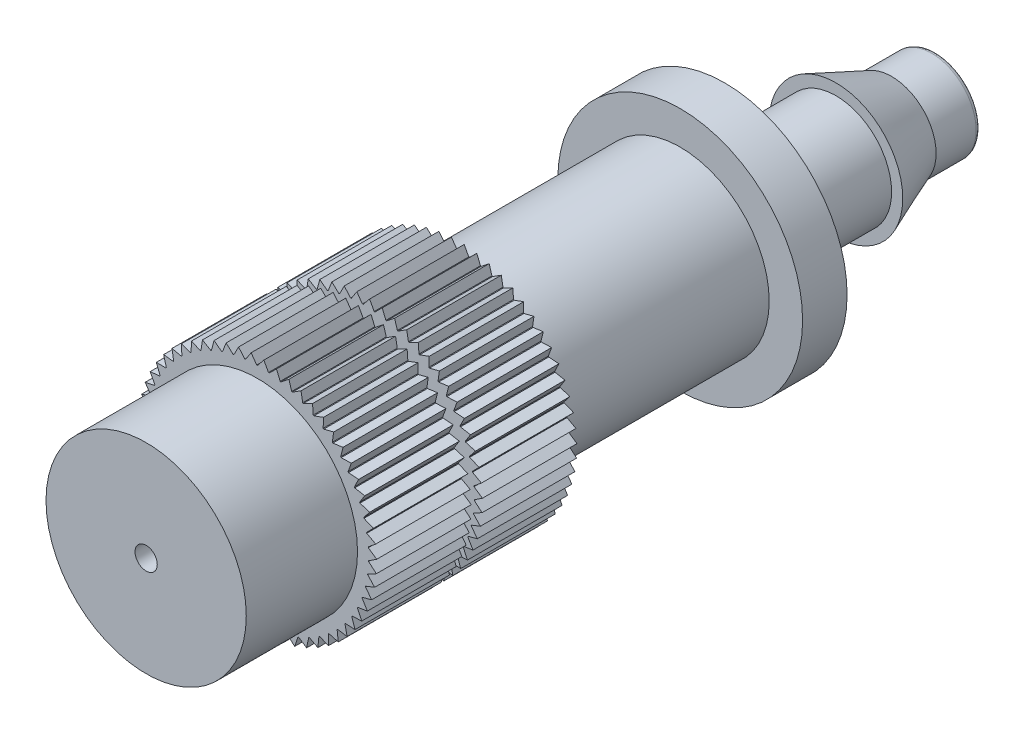
SolidWorks part; units mm, degrees
material "ABS"
ref_plane "Front Plane" through (0, 0, 0) normal (0, 0, 1) x (1, 0, 0)
ref_plane "Top Plane" through (0, 0, 0) normal (0, 1, 0) x (1, 0, 0)
ref_plane "Right Plane" through (0, 0, 0) normal (1, 0, 0) x (0, 0, -1)
sketch "Sketch1" plane through (0, 0, 0) normal (0, 0, 1) x (1, 0, 0)
  circle A0 centre (0, 0) radius 2
  dimension "D1" = 4
extrude "Boss-Extrude1" add sketch "Sketch1" along normal blind 2
sketch "Sketch3" plane through (0, 0, 0) normal (0, 1, 0) x (1, 0, 0)
  line L0 (0, -4.5) -> (0, -2)
  line L1 (-2, -2) -> (2, -2) construction
  line L2 (0, -2) -> (-2, -2)
  line L3 (-2, -2) -> (-3, -4.5)
  line L4 (-3, -4.5) -> (0, -4.5)
  dimension "D1" = 2.5
  dimension "D2" = 3
revolve "Revolve1" add sketch "Sketch3" angle 360 about L0
sketch "Sketch4" plane through (0, 0, 4.5) normal (0, 0, 1) x (1, 0, 0)
  circle A0 centre (0, 0) radius 2.5
  dimension "D1" = 5
extrude "Boss-Extrude2" add sketch "Sketch4" along normal blind 5
sketch "Sketch5" plane through (0, 0, 9.5) normal (0, 0, 1) x (1, 0, 0)
  circle A0 centre (0, 0) radius 5.5
  dimension "D1" = 11
extrude "Boss-Extrude3" add sketch "Sketch5" along normal blind 2
sketch "Sketch6" plane through (0, 0, 11.5) normal (0, 0, 1) x (1, 0, 0)
  circle A0 centre (0, 0) radius 4
  dimension "D1" = 8
extrude "Boss-Extrude4" add sketch "Sketch6" along normal blind 10
sketch "Sketch7" plane through (0, 0, 21.5) normal (0, 0, 1) x (1, 0, 0)
  line L0 (0, 5) -> (0.291, 5.3547)
  line L1 (0.291, 5.3547) -> (0.4994, 4.975)
  line L2 (0, 5) -> (0.4994, 4.975)
  line L3 (0.5315, 4.9717) -> (1.0254, 4.8937)
  line L4 (0.8586, 5.2934) -> (1.0254, 4.8937)
  line L5 (0.5315, 4.9717) -> (0.8586, 5.2934)
  line L6 (1.0569, 4.887) -> (1.5397, 4.757)
  line L7 (1.4163, 5.1722) -> (1.5397, 4.757)
  line L8 (1.0569, 4.887) -> (1.4163, 5.1722)
  line L9 (1.5704, 4.747) -> (2.0366, 4.5664)
  line L10 (1.9581, 4.9923) -> (2.0366, 4.5664)
  line L11 (1.5704, 4.747) -> (1.9581, 4.9923)
  line L12 (2.0661, 4.5532) -> (2.5105, 4.3241)
  line L13 (2.4777, 4.7559) -> (2.5105, 4.3241)
  line L14 (2.0661, 4.5532) -> (2.4777, 4.7559)
  line L15 (2.5383, 4.3078) -> (2.9559, 4.0327)
  line L16 (2.9691, 4.4656) -> (2.9559, 4.0327)
  line L17 (2.5383, 4.3078) -> (2.9691, 4.4656)
  line L18 (2.9818, 4.0136) -> (3.3678, 3.6957)
  line L19 (3.427, 4.1247) -> (3.3678, 3.6957)
  line L20 (2.9818, 4.0136) -> (3.427, 4.1247)
  line L21 (3.3916, 3.6739) -> (3.7415, 3.3168)
  line L22 (3.846, 3.7371) -> (3.7415, 3.3168)
  line L23 (3.3916, 3.6739) -> (3.846, 3.7371)
  line L24 (3.7629, 3.2926) -> (4.0729, 2.9003)
  line L25 (4.2214, 3.3071) -> (4.0729, 2.9003)
  line L26 (3.7629, 3.2926) -> (4.2214, 3.3071)
  line L27 (4.0915, 2.8739) -> (4.3581, 2.4509)
  line L28 (4.5491, 2.8397) -> (4.3581, 2.4509)
  line L29 (4.0915, 2.8739) -> (4.5491, 2.8397)
  line L30 (4.3738, 2.4228) -> (4.5939, 1.9738)
  line L31 (4.8251, 2.34) -> (4.5939, 1.9738)
  line L32 (4.3738, 2.4228) -> (4.8251, 2.34)
  line L33 (4.6066, 1.9441) -> (4.7777, 1.4743)
  line L34 (5.0465, 1.8139) -> (4.7777, 1.4743)
  line L35 (4.6066, 1.9441) -> (5.0465, 1.8139)
  line L36 (4.7871, 1.4435) -> (4.9073, 0.9581)
  line L37 (5.2107, 1.2672) -> (4.9073, 0.9581)
  line L38 (4.7871, 1.4435) -> (5.2107, 1.2672)
  line L39 (4.9134, 0.9264) -> (4.9814, 0.4311)
  line L40 (5.3159, 0.7062) -> (4.9814, 0.4311)
  line L41 (4.9134, 0.9264) -> (5.3159, 0.7062)
  line L42 (4.9841, 0.3989) -> (4.999, -0.1008)
  line L43 (5.3609, 0.1371) -> (4.999, -0.1008)
  line L44 (4.9841, 0.3989) -> (5.3609, 0.1371)
  line L45 (4.9982, -0.1331) -> (4.9599, -0.6316)
  line L46 (5.3451, -0.4335) -> (4.9599, -0.6316)
  line L47 (4.9982, -0.1331) -> (5.3451, -0.4335)
  line L48 (4.9558, -0.6636) -> (4.8647, -1.1553)
  line L49 (5.2687, -0.9992) -> (4.8647, -1.1553)
  line L50 (4.9558, -0.6636) -> (5.2687, -0.9992)
  line L51 (4.8571, -1.1866) -> (4.7143, -1.6658)
  line L52 (5.1327, -1.5535) -> (4.7143, -1.6658)
  line L53 (4.8571, -1.1866) -> (5.1327, -1.5535)
  line L54 (4.7035, -1.6962) -> (4.5106, -2.1575)
  line L55 (4.9384, -2.0903) -> (4.5106, -2.1575)
  line L56 (4.7035, -1.6962) -> (4.9384, -2.0903)
  line L57 (4.4966, -2.1865) -> (4.2557, -2.6247)
  line L58 (4.6883, -2.6034) -> (4.2557, -2.6247)
  line L59 (4.4966, -2.1865) -> (4.6883, -2.6034)
  line L60 (4.2387, -2.6521) -> (3.9526, -3.0622)
  line L61 (4.385, -3.087) -> (3.9526, -3.0622)
  line L62 (4.2387, -2.6521) -> (4.385, -3.087)
  line L63 (3.9328, -3.0876) -> (3.6047, -3.465)
  line L64 (4.032, -3.5356) -> (3.6047, -3.465)
  line L65 (3.9328, -3.0876) -> (4.032, -3.5356)
  line L66 (3.5823, -3.4882) -> (3.216, -3.8285)
  line L67 (3.6334, -3.9441) -> (3.216, -3.8285)
  line L68 (3.5823, -3.4882) -> (3.6334, -3.9441)
  line L69 (3.1912, -3.8492) -> (2.7908, -4.1486)
  line L70 (3.1936, -4.308) -> (2.7908, -4.1486)
  line L71 (3.1912, -3.8492) -> (3.1936, -4.308)
  line L72 (2.764, -4.1666) -> (2.334, -4.4218)
  line L73 (2.7176, -4.623) -> (2.334, -4.4218)
  line L74 (2.764, -4.1666) -> (2.7176, -4.623)
  line L75 (2.3055, -4.4368) -> (1.8508, -4.6448)
  line L76 (2.2108, -4.8857) -> (1.8508, -4.6448)
  line L77 (2.3055, -4.4368) -> (2.2108, -4.8857)
  line L78 (1.8208, -4.6567) -> (1.3466, -4.8153)
  line L79 (1.6789, -5.093) -> (1.3466, -4.8153)
  line L80 (1.8208, -4.6567) -> (1.6789, -5.093)
  line L81 (1.3155, -4.8238) -> (0.8272, -4.9311)
  line L82 (1.1281, -5.2426) -> (0.8272, -4.9311)
  line L83 (1.3155, -4.8238) -> (1.1281, -5.2426)
  line L84 (0.7953, -4.9363) -> (0.2983, -4.9911)
  line L85 (0.5644, -5.3328) -> (0.2983, -4.9911)
  line L86 (0.7953, -4.9363) -> (0.5644, -5.3328)
  line L87 (0.2661, -4.9929) -> (-0.2339, -4.9945)
  line L88 (-0.0056, -5.3626) -> (-0.2339, -4.9945)
  line L89 (0.2661, -4.9929) -> (-0.0056, -5.3626)
  line L90 (-0.2661, -4.9929) -> (-0.7634, -4.9414)
  line L91 (-0.5756, -5.3316) -> (-0.7634, -4.9414)
  line L92 (-0.2661, -4.9929) -> (-0.5756, -5.3316)
  line L93 (-0.7953, -4.9363) -> (-1.2844, -4.8322)
  line L94 (-1.1391, -5.2402) -> (-1.2844, -4.8322)
  line L95 (-0.7953, -4.9363) -> (-1.1391, -5.2402)
  line L96 (-1.3155, -4.8238) -> (-1.7907, -4.6683)
  line L97 (-1.6896, -5.0895) -> (-1.7907, -4.6683)
  line L98 (-1.3155, -4.8238) -> (-1.6896, -5.0895)
  line L99 (-1.8208, -4.6567) -> (-2.2768, -4.4515)
  line L100 (-2.221, -4.8811) -> (-2.2768, -4.4515)
  line L101 (-1.8208, -4.6567) -> (-2.221, -4.8811)
  line L102 (-2.3055, -4.4368) -> (-2.7371, -4.1843)
  line L103 (-2.7273, -4.6173) -> (-2.7371, -4.1843)
  line L104 (-2.3055, -4.4368) -> (-2.7273, -4.6173)
  line L105 (-2.764, -4.1666) -> (-3.1663, -3.8697)
  line L106 (-3.2026, -4.3013) -> (-3.1663, -3.8697)
  line L107 (-2.764, -4.1666) -> (-3.2026, -4.3013)
  line L108 (-3.1912, -3.8492) -> (-3.5597, -3.5112)
  line L109 (-3.6417, -3.9365) -> (-3.5597, -3.5112)
  line L110 (-3.1912, -3.8492) -> (-3.6417, -3.9365)
  line L111 (-3.5823, -3.4882) -> (-3.9128, -3.1129)
  line L112 (-4.0394, -3.5271) -> (-3.9128, -3.1129)
  line L113 (-3.5823, -3.4882) -> (-4.0394, -3.5271)
  line L114 (-3.9328, -3.0876) -> (-4.2215, -2.6794)
  line L115 (-4.3915, -3.0778) -> (-4.2215, -2.6794)
  line L116 (-3.9328, -3.0876) -> (-4.3915, -3.0778)
  line L117 (-4.2387, -2.6521) -> (-4.4824, -2.2155)
  line L118 (-4.6937, -2.5935) -> (-4.4824, -2.2155)
  line L119 (-4.2387, -2.6521) -> (-4.6937, -2.5935)
  line L120 (-4.4966, -2.1865) -> (-4.6925, -1.7265)
  line L121 (-4.9428, -2.0799) -> (-4.6925, -1.7265)
  line L122 (-4.4966, -2.1865) -> (-4.9428, -2.0799)
  line L123 (-4.7035, -1.6962) -> (-4.8494, -1.218)
  line L124 (-5.1359, -1.5428) -> (-4.8494, -1.218)
  line L125 (-4.7035, -1.6962) -> (-5.1359, -1.5428)
  line L126 (-4.8571, -1.1866) -> (-4.9514, -0.6956)
  line L127 (-5.2708, -0.9881) -> (-4.9514, -0.6956)
  line L128 (-4.8571, -1.1866) -> (-5.2708, -0.9881)
  line L129 (-4.9558, -0.6636) -> (-4.9973, -0.1654)
  line L130 (-5.346, -0.4223) -> (-4.9973, -0.1654)
  line L131 (-4.9558, -0.6636) -> (-5.346, -0.4223)
  line L132 (-4.9982, -0.1331) -> (-4.9865, 0.3668)
  line L133 (-5.3606, 0.1484) -> (-4.9865, 0.3668)
  line L134 (-4.9982, -0.1331) -> (-5.3606, 0.1484)
  line L135 (-4.9841, 0.3989) -> (-4.9193, 0.8947)
  line L136 (-5.3144, 0.7173) -> (-4.9193, 0.8947)
  line L137 (-4.9841, 0.3989) -> (-5.3144, 0.7173)
  line L138 (-4.9134, 0.9264) -> (-4.7963, 1.4125)
  line L139 (-5.2081, 1.2782) -> (-4.7963, 1.4125)
  line L140 (-4.9134, 0.9264) -> (-5.2081, 1.2782)
  line L141 (-4.7871, 1.4435) -> (-4.619, 1.9144)
  line L142 (-5.0427, 1.8245) -> (-4.619, 1.9144)
  line L143 (-4.7871, 1.4435) -> (-5.0427, 1.8245)
  line L144 (-4.6066, 1.9441) -> (-4.3894, 2.3945)
  line L145 (-4.8202, 2.3502) -> (-4.3894, 2.3945)
  line L146 (-4.6066, 1.9441) -> (-4.8202, 2.3502)
  line L147 (-4.3738, 2.4228) -> (-4.11, 2.8475)
  line L148 (-4.5431, 2.8492) -> (-4.11, 2.8475)
  line L149 (-4.3738, 2.4228) -> (-4.5431, 2.8492)
  line L150 (-4.0915, 2.8739) -> (-3.784, 3.2682)
  line L151 (-4.2145, 3.316) -> (-3.784, 3.2682)
  line L152 (-4.0915, 2.8739) -> (-4.2145, 3.316)
  line L153 (-3.7629, 3.2926) -> (-3.4152, 3.6519)
  line L154 (-3.8382, 3.7452) -> (-3.4152, 3.6519)
  line L155 (-3.7629, 3.2926) -> (-3.8382, 3.7452)
  line L156 (-3.3916, 3.6739) -> (-3.0077, 3.9942)
  line L157 (-3.4183, 4.1319) -> (-3.0077, 3.9942)
  line L158 (-3.3916, 3.6739) -> (-3.4183, 4.1319)
  line L159 (-2.9818, 4.0136) -> (-2.5661, 4.2913)
  line L160 (-2.9598, 4.4718) -> (-2.5661, 4.2913)
  line L161 (-2.9818, 4.0136) -> (-2.9598, 4.4718)
  line L162 (-2.5383, 4.3078) -> (-2.0954, 4.5397)
  line L163 (-2.4677, 4.7611) -> (-2.0954, 4.5397)
  line L164 (-2.5383, 4.3078) -> (-2.4677, 4.7611)
  line L165 (-2.0661, 4.5532) -> (-1.601, 4.7368)
  line L166 (-1.9476, 4.9964) -> (-1.601, 4.7368)
  line L167 (-2.0661, 4.5532) -> (-1.9476, 4.9964)
  line L168 (-1.5704, 4.747) -> (-1.0884, 4.8801)
  line L169 (-1.4055, 5.1752) -> (-1.0884, 4.8801)
  line L170 (-1.5704, 4.747) -> (-1.4055, 5.1752)
  line L171 (-1.0569, 4.887) -> (-0.5635, 4.9681)
  line L172 (-0.8474, 5.2952) -> (-0.5635, 4.9681)
  line L173 (-1.0569, 4.887) -> (-0.8474, 5.2952)
  line L174 (-0.5315, 4.9717) -> (-0.0323, 4.9999)
  line L175 (-0.2798, 5.3553) -> (-0.0323, 4.9999)
  line L176 (-0.5315, 4.9717) -> (-0.2798, 5.3553)
  circle A0 centre (0, 0) radius 5
  point P90 (0, 0)
  circle M2 centre (0, 0) radius 4
  dimension "D1" = 10
  dimension "D2" = 0.5
  dimension "D3" = 59
fillet "Fillet2" radius 0.2 1 edges at (2, 0, 0)
extrude "Boss-Extrude5" add sketch "Sketch7" along normal blind 9 contours A0 L172 L173 | A0 L166 L167 | A0 L175 L176 | A0 L1 L0 | A0 L13 L14 | A0 L19 L20 | A0 L16 L17 | A0 L22 L23 | A0 L25 L26 | A0 L28 L29 | A0 L31 L32 | A0 L40 L41 | A0 L43 L44 | A0 L46 L47 | A0 L52 L53 | A0 L55 L56 | A0 L58 L59 | A0 L61 L62 | A0 L64 L65 | A0 L163 L164 | A0 L160 L161 | A0 L157 L158 | A0 L154 L155 | A0 L151 L152 | A0 L148 L149 | A0 L142 L143 | A0 L139 L140 | A0 L136 L137 | A0 L133 L134 | A0 L130 L131 | A0 L127 L128 | A0 L112 L113 | A0 L115 L116 | A0 L118 L119 | A0 L121 L122 | A0 L124 L125 | A0 L109 L110 | A0 L106 L107 | A0 L103 L104 | A0 L100 L101 | A0 L97 L98 | A0 L91 L92 | A0 L85 L86 | A0 L82 L83 | A0 L79 L80 | A0 L76 L77 | A0 L73 L74 | A0 L70 L71 | A0 L67 L68 | L42 A0 L39 L36 L33 L30 L27 L24 L21 L18 L15 L12 L9 L6 L3 L2 L174 L171 L168 L165 L162 L159 L156 L153 L150 L147 L144 | M2 | L168 L169 L170 | L4 L3 L5 | L7 L6 L8 | L10 L9 L11 | L33 L34 L35 | L36 L37 L38 | L48 L49 L50 | L145 L144 L146 | L93 L94 L95 | A0 | L87 L88 L89 region at (0.2638, 5.1127, 21.5) region at (0.2426, 4.8463, 21.5) region at (-0.2812, 5.1118, 21.5) region at (-0.8229, 5.0529, 21.5) region at (-1.8724, 4.7648, 21.5) region at (2.3528, 4.5468, 21.5) region at (-2.3683, 4.5388, 21.5) region at (2.8228, 4.2709, 21.5) region at (-2.8373, 4.2613, 21.5) region at (3.2608, 3.9467, 21.5) region at (-3.2742, 3.9356, 21.5) region at (3.6618, 3.5777, 21.5) region at (-3.6739, 3.5653, 21.5) region at (4.0214, 3.1682, 21.5) region at (-4.0321, 3.1546, 21.5) region at (4.3353, 2.7228, 21.5) region at (-4.3446, 2.7081, 21.5) region at (4.6002, 2.2466, 21.5) region at (-4.8188, 1.7285, 21.5) region at (-4.9753, 1.2065, 21.5) region at (5.073, 0.6881, 21.5) region at (-5.0753, 0.6709, 21.5) region at (5.1174, 0.145, 21.5) region at (-5.1179, 0.1276, 21.5) region at (5.1038, -0.3998, 21.5) region at (-5.1025, -0.4171, 21.5) region at (-5.0292, -0.9571, 21.5) region at (4.904, -1.4696, 21.5) region at (-4.899, -1.4863, 21.5) region at (4.72, -1.9826, 21.5) region at (-4.7132, -1.9986, 21.5) region at (4.4825, -2.473, 21.5) region at (-4.4741, -2.4883, 21.5) region at (4.1943, -2.9355, 21.5) region at (-4.1843, -2.9497, 21.5) region at (3.8585, -3.3647, 21.5) region at (-3.847, -3.3778, 21.5) region at (3.479, -3.7558, 21.5) region at (-3.4662, -3.7676, 21.5) region at (3.0601, -4.1043, 21.5) region at (-3.0461, -4.1146, 21.5) region at (2.6065, -4.4063, 21.5) region at (-2.5915, -4.4151, 21.5) region at (2.1233, -4.6584, 21.5) region at (-2.1075, -4.6656, 21.5) region at (1.6162, -4.8577, 21.5) region at (-1.5996, -4.8631, 21.5) region at (1.0907, -5.0019, 21.5) region at (0.5528, -5.0895, 21.5) region at (-0.5355, -5.0914, 21.5) region at (0, 0, 21.5)
ref_plane "Plane1" through (0, 0, 26) normal (0, 0, 1) x (1, 0, 0)
sketch "Sketch8" plane through (0, 0, 26) normal (0, 0, 1) x (1, 0, 0)
  circle A0 centre (0, 0) radius 4
  circle A1 centre (0, 0) radius 5.4669
  dimension "8" = 8
extrude "Cut-Extrude1" cut sketch "Sketch8" against normal mid plane 0.5
sketch "Sketch9" plane through (0, 0, 30.5) normal (0, 0, 1) x (1, 0, 0)
  circle A0 centre (0, 0) radius 4.5
  dimension "D1" = 9
extrude "Boss-Extrude6" add sketch "Sketch9" along normal blind 5
sketch "Sketch10" plane through (0, 0, 0) normal (0, 0, -1) x (-1, 0, 0)
  circle A0 centre (0, 0) radius 1.75
  dimension "D1" = 3.5
extrude "Cut-Extrude2" cut sketch "Sketch10" against normal blind 33.5
sketch "Sketch11" plane through (0, 0, 35.5) normal (0, 0, 1) x (1, 0, 0)
  circle A0 centre (0, 0) radius 0.5
  dimension "D1" = 1
extrude "Cut-Extrude3" cut sketch "Sketch11" against normal blind 1
